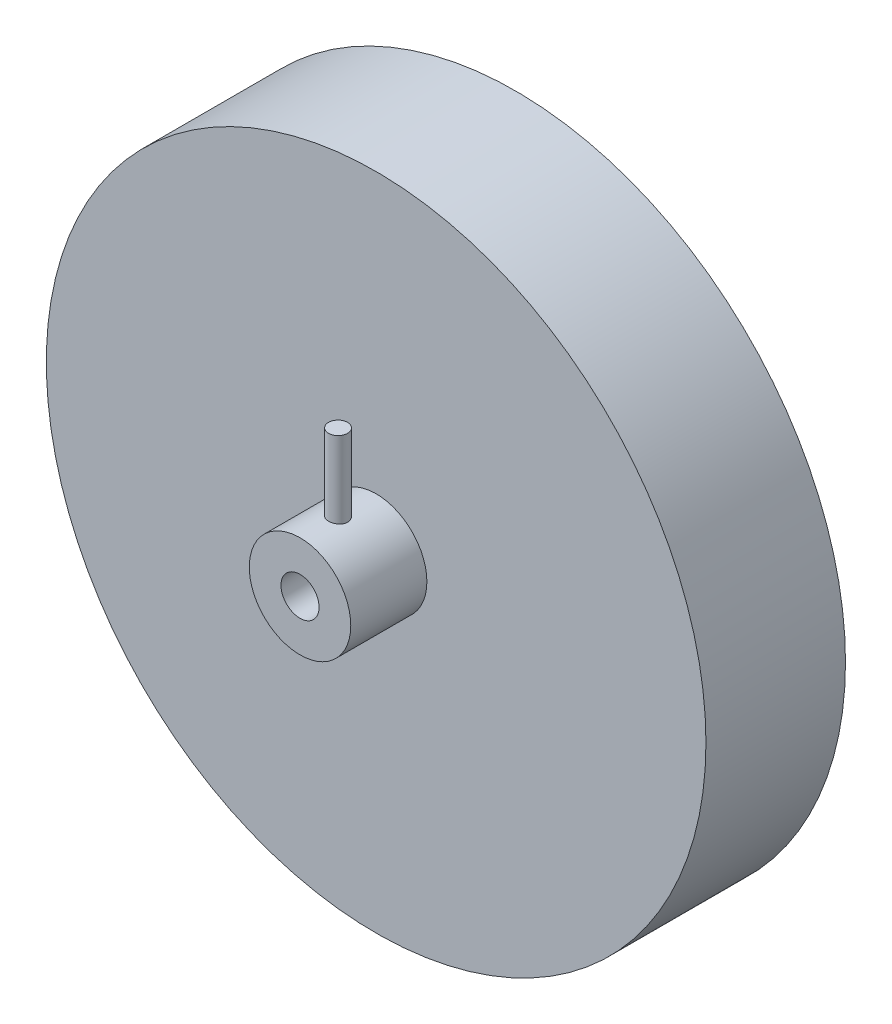
SolidWorks part; units mm, degrees
ref_plane "Front Plane" through (0, 0, 0) normal (0, 0, 1) x (1, 0, 0)
ref_plane "Top Plane" through (0, 0, 0) normal (0, 1, 0) x (1, 0, 0)
ref_plane "Right Plane" through (0, 0, 0) normal (1, 0, 0) x (0, 0, -1)
sketch "Sketch1" plane through (0, 0, 0) normal (0, 0, 1) x (1, 0, 0)
  circle A0 centre (0, 0) radius 52
  dimension "D1" = 104
extrude "Boss-Extrude1" add sketch "Sketch1" along normal mid plane 22
sketch "Sketch2" plane through (0, 0, 11) normal (0, 0, 1) x (1, 0, 0)
  circle A0 centre (0, 0) radius 8
  dimension "D1" = 16
extrude "Boss-Extrude2" add sketch "Sketch2" along normal blind 12
sketch "Sketch3" plane through (0, 0, 0) normal (0, 1, 0) x (1, 0, 0)
  line L1 (8, -23) -> (8, -11) construction
  line L3 (-8, -17) -> (8, -17) construction
  line L4 (-8, -11) -> (-8, -23) construction
  line L5 (0, -22.2086) -> (0, 0) construction
  circle A0 centre (0, -17) radius 1.5
  point P6 (-2.631, -15.557)
  dimension "D1" = 3
extrude "Boss-Extrude3" add sketch "Sketch3" along normal blind 20
sketch "Sketch4" plane through (0, 0, 23) normal (0, 0, -1) x (-1, 0, 0)
  circle A0 centre (0, 0) radius 3
  dimension "D1" = 6
extrude "Cut-Extrude3" cut sketch "Sketch4" along normal blind 12
